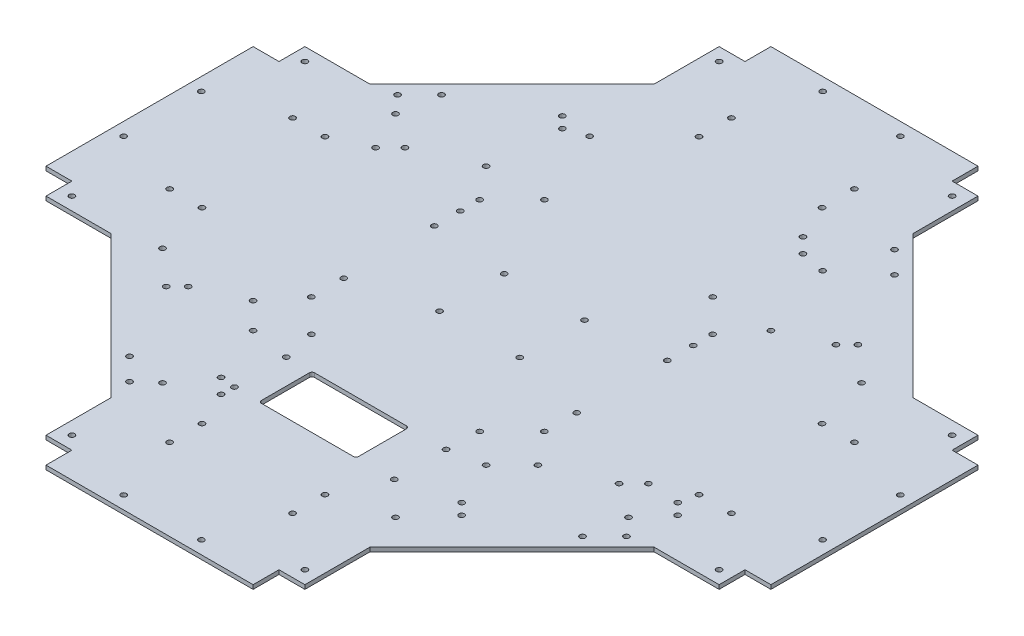
SolidWorks part; units mm, degrees
ref_plane "Front Plane" through (0, 0, 0) normal (0, 0, 1) x (1, 0, 0)
ref_plane "Top Plane" through (0, 0, 0) normal (0, 1, 0) x (1, 0, 0)
ref_plane "Right Plane" through (0, 0, 0) normal (1, 0, 0) x (0, 0, -1)
sketch "Sketch1" plane through (0, 0, 0) normal (0, 1, 0) x (1, 0, 0)
  line L0 (0, -280) -> (100, -280)
  line L1 (100, -280) -> (100, -209.6016)
  line L2 (280, -100) -> (209.6016, -100)
  line L3 (0, 0) -> (0, -280) construction
  line L4 (280, 0) -> (280, -100)
  line L5 (-280, 280) -> (280, 280) construction
  line L6 (-280, 280) -> (-280, -280) construction
  line L7 (-280, -280) -> (280, -280) construction
  line L8 (280, 280) -> (280, -280) construction
  line L9 (-280, 280) -> (280, -280) construction
  line L10 (-280, -280) -> (280, 280) construction
  line L11 (100, -209.6016) -> (209.6016, -100)
  line L12 (-280, 0) -> (-280, -100)
  line L13 (-280, -100) -> (-209.6016, -100)
  line L14 (-209.6016, -100) -> (-100, -209.6016)
  line L15 (-100, -280) -> (-100, -209.6016)
  line L16 (0, -280) -> (-100, -280)
  line L17 (0, 280) -> (-100, 280)
  line L18 (-100, 280) -> (-100, 209.6016)
  line L19 (-100, 209.6016) -> (-209.6016, 100)
  line L20 (-280, 100) -> (-209.6016, 100)
  line L21 (-280, 0) -> (-280, 100)
  line L22 (280, 0) -> (280, 100)
  line L23 (280, 100) -> (209.6016, 100)
  line L24 (209.6016, 100) -> (100, 209.6016)
  line L25 (100, 280) -> (100, 209.6016)
  line L26 (0, 280) -> (100, 280)
  line L27 (111.5258, -219.2889) -> (219.2889, -111.5258) construction
  line L28 (219.2889, -111.5258) -> (247.5732, -139.8101) construction
  line L29 (247.5732, -139.8101) -> (139.8101, -247.5732) construction
  line L30 (139.8101, -247.5732) -> (111.5258, -219.2889) construction
  line L31 (-100, -270) -> (100, -270) construction
  line L32 (-90, -280) -> (-90, 280) construction
  line L33 (-75, -75) -> (75, -75) construction
  line L34 (-75, -75) -> (-75, 75) construction
  line L35 (-75, 75) -> (75, 75) construction
  line L36 (75, -75) -> (75, 75) construction
  line L37 (-75, -75) -> (75, 75) construction
  line L38 (-75, 75) -> (75, -75) construction
  line L39 (-100, -260) -> (100, -260) construction
  line L40 (-280, 40) -> (280, 40) construction
  line L41 (0, 280) -> (0, 0) construction
  line L42 (-280, -90) -> (280, -90) construction
  line L43 (-260, -100) -> (-260, 100) construction
  line L44 (0, 0) -> (-280, 0) construction
  arc A0 (100, -280) -> (280, -100) centre (100, -100) ccw construction
  circle A1 centre (-47.5, -192) radius 2.125
  circle A2 centre (-47.5, -217) radius 2.125
  circle A3 centre (47.5, -217) radius 2.125
  circle A4 centre (47.5, -192) radius 2.125
  circle A5 centre (-192, 47.5) radius 2.125
  circle A6 centre (-217, 47.5) radius 2.125
  circle A7 centre (-192, -47.5) radius 2.125
  circle A8 centre (-217, -47.5) radius 2.125
  circle A9 centre (47.5, 192) radius 2.125
  circle A10 centre (47.5, 217) radius 2.125
  circle A11 centre (-47.5, 192) radius 2.125
  circle A12 centre (-47.5, 217) radius 2.125
  circle A13 centre (192, -47.5) radius 2.125
  circle A14 centre (217, -47.5) radius 2.125
  circle A15 centre (192, 47.5) radius 2.125
  circle A16 centre (217, 47.5) radius 2.125
  circle A17 centre (-90, -270) radius 2.125
  circle A18 centre (-30, -270) radius 2.125
  circle A19 centre (30, -270) radius 2.125
  circle A20 centre (90, -270) radius 2.125
  circle A21 centre (-270, 90) radius 2.125
  circle A22 centre (-270, 30) radius 2.125
  circle A23 centre (-270, -30) radius 2.125
  circle A24 centre (-270, -90) radius 2.125
  circle A25 centre (90, 270) radius 2.125
  circle A26 centre (30, 270) radius 2.125
  circle A27 centre (-30, 270) radius 2.125
  circle A28 centre (-90, 270) radius 2.125
  circle A29 centre (270, -90) radius 2.125
  circle A30 centre (270, -30) radius 2.125
  circle A31 centre (270, 30) radius 2.125
  circle A32 centre (270, 90) radius 2.125
  circle A33 centre (-90, -250) radius 2.125
  circle A34 centre (-90, -180) radius 2.125
  circle A35 centre (-90, -110) radius 2.125
  circle A36 centre (-90, -40) radius 2.125
  circle A37 centre (-90, 30) radius 2.125
  circle A38 centre (-90, 50) radius 2.125
  circle A39 centre (-90, 100) radius 2.125 construction
  circle A40 centre (-90, 150) radius 2.125
  circle A41 centre (-90, 200) radius 2.125 construction
  circle A42 centre (-90, 250) radius 2.125
  circle A43 centre (90, -250) radius 2.125
  circle A44 centre (90, -180) radius 2.125
  circle A45 centre (90, -110) radius 2.125
  circle A46 centre (90, -40) radius 2.125
  circle A47 centre (90, 30) radius 2.125
  circle A48 centre (90, 50) radius 2.125
  circle A49 centre (90, 100) radius 2.125 construction
  circle A50 centre (90, 150) radius 2.125
  circle A51 centre (90, 200) radius 2.125 construction
  circle A52 centre (90, 250) radius 2.125
  circle A53 centre (-250, -90) radius 2.125
  circle A54 centre (-180, -90) radius 2.125
  circle A55 centre (-110, -90) radius 2.125
  circle A56 centre (-110, 90) radius 2.125
  circle A57 centre (-180, 90) radius 2.125
  circle A58 centre (-250, 90) radius 2.125
  circle A59 centre (110, -90) radius 2.125
  circle A60 centre (180, -90) radius 2.125
  circle A61 centre (250, -90) radius 2.125
  circle A62 centre (110, 90) radius 2.125
  circle A63 centre (180, 90) radius 2.125
  circle A64 centre (250, 90) radius 2.125
  point P33 (0, 0)
  point P68 (0, 0)
  point P107 (0, 0)
  dimension "D10" = 25
  dimension "4.25" = 4.25
  dimension "D11" = 4.25
  dimension "D16" = 4.25
  dimension "D24" = 4.25
  dimension "D28" = 4.25
  dimension "D32" = 4.25
  dimension "D1" = 560
  dimension "D2" = 90
  dimension "D3" = 280
  dimension "D4" = 4
  dimension "D5" = 100
  dimension "D6" = 155
  dimension "D7" = 152.4
  dimension "D8" = 15
  dimension "D9" = 40
  dimension "D12" = 47.5
  dimension "D13" = 63
  dimension "D15" = 10
  dimension "D17" = 10
  dimension "D18" = 76.2
  dimension "D19" = 150
  dimension "D20" = 150
  dimension "D23" = 10
  dimension "D25" = 10
  dimension "D26" = 300
  dimension "D29" = 10
  dimension "D31" = 20
  dimension "D33" = 10
  dimension "D21" = 4
  dimension "D27" = 5
  dimension "D30" = 5
  dimension "D34" = 3
  dimension "D14" = 4
  dimension "D22" = 4
extrude "Boss-Extrude1" add sketch "Sketch1" along normal blind 3.175 contours L26 L17 L18 L19 L20 L21 L12 L13 L14 L15 L16 L0 L1 L11 L2 L4 L22 L23 L24 L25 region at (0, 0, -0.0137)
sketch "Sketch2" plane through (0, 3.175, 0) normal (0, 1, 0) x (1, 0, 0)
  line L0 (0, 25.5202) -> (0, -25) construction
  line L1 (-31, -25) -> (31, -25) construction
  line L2 (-31, -25) -> (-31, 25) construction
  line L3 (-31, 25) -> (31, 25) construction
  line L4 (31, -25) -> (31, 25) construction
  line L5 (-31, -25) -> (31, 25) construction
  line L6 (-31, 25) -> (31, -25) construction
  line L7 (75, -75) -> (75, 75) construction
  line L8 (-75, -75) -> (75, -75) construction
  line L9 (-75, -75) -> (-75, 75) construction
  line L10 (-75, 75) -> (75, 75) construction
  line L11 (75, -75) -> (75, 75) construction
  line L12 (-75, -75) -> (75, -75) construction
  line L13 (-75, -75) -> (-75, 75) construction
  line L14 (-75, 75) -> (75, 75) construction
  line L15 (-90, 270) -> (-90, -270) construction
  line L16 (-270, 90) -> (270, 90) construction
  line L17 (-40.0349, -135) -> (34.9651, -135) construction
  line L18 (-40.0349, -155.5) -> (34.9651, -155.5)
  line L19 (-40.0349, -155.5) -> (-40.0349, -114.5)
  line L20 (-40.0349, -114.5) -> (34.9651, -114.5)
  line L21 (34.9651, -155.5) -> (34.9651, -114.5)
  line L22 (-40.0349, -155.5) -> (34.9651, -114.5) construction
  line L23 (-40.0349, -114.5) -> (34.9651, -155.5) construction
  line L24 (153.737, -71.0118) -> (187.3311, -37.4177) construction
  line L25 (128.2843, -167.1751) -> (80.1718, -119.0627) construction
  line L26 (92.9289, -202.5305) -> (202.5305, -92.9289)
  line L27 (92.9289, -202.5305) -> (202.5305, -92.9289) construction
  line L28 (170.0036, -125.4558) -> (128.4969, -83.9492) construction
  circle A0 centre (-31, 25) radius 2.125
  circle A1 centre (-31, -25) radius 2.125
  circle A2 centre (31, -25) radius 2.125
  circle A3 centre (31, 25) radius 2.125
  circle A4 centre (-90, 65) radius 2.125
  circle A5 centre (-65, 90) radius 2.125
  circle A6 centre (65, 90) radius 2.125
  circle A7 centre (90, 65) radius 2.125
  circle A8 centre (90, -65) radius 2.125
  circle A9 centre (65, -90) radius 2.125
  circle A10 centre (-65, -90) radius 2.125
  circle A11 centre (-90, -65) radius 2.125
  circle A12 centre (64.0651, -115) radius 2.125
  circle A13 centre (64.0651, -155) radius 2.125
  circle A14 centre (-59.4349, -115) radius 2.125
  circle A15 centre (-59.4349, -155) radius 2.125
  circle A16 centre (174.9533, -120.5061) radius 2.125
  circle A17 centre (191.9239, -103.5355) radius 2.125
  circle A18 centre (153.737, -71.0118) radius 2.125
  circle A19 centre (165.0507, -59.6981) radius 2.125
  circle A20 centre (-71.0118, -153.737) radius 2.125
  circle A21 centre (-59.6981, -165.0507) radius 2.125
  circle A22 centre (-120.5061, -174.9533) radius 2.125
  circle A23 centre (-103.5355, -191.9239) radius 2.125
  circle A24 centre (-153.737, 71.0118) radius 2.125
  circle A25 centre (-165.0507, 59.6981) radius 2.125
  circle A26 centre (-174.9533, 120.5061) radius 2.125
  circle A27 centre (-191.9239, 103.5355) radius 2.125
  circle A28 centre (71.0118, 153.737) radius 2.125
  circle A29 centre (59.6981, 165.0507) radius 2.125
  circle A30 centre (120.5061, 174.9533) radius 2.125
  circle A31 centre (103.5355, 191.9239) radius 2.125
  circle A32 centre (114.1421, -153.033) radius 2.125
  circle A33 centre (105.6569, -144.5477) radius 2.125
  circle A34 centre (-144.5477, -105.6569) radius 2.125
  circle A35 centre (-153.033, -114.1421) radius 2.125
  circle A36 centre (-105.6569, 144.5477) radius 2.125
  circle A37 centre (-114.1421, 153.033) radius 2.125
  circle A38 centre (144.5477, 105.6569) radius 2.125
  circle A39 centre (153.033, 114.1421) radius 2.125
  circle A40 centre (197.5807, -69.5944) radius 2.125
  circle A41 centre (189.0955, -61.1091) radius 2.125
  point P0 (0, 0)
  point P28 (-2.5349, -135)
  point P43 (0, 0)
  point P94 (0, 0)
  point P113 (0, 0)
  dimension "D3" = 4.25
  dimension "D4" = 4.25
  dimension "D5" = 4.25
  dimension "D7" = 4.25
  dimension "D13" = 4.25
  dimension "D16" = 4.25
  dimension "D20" = 4.25
  dimension "D22" = 4.25
  dimension "D25" = 4.25
  dimension "D26" = 53.85
  dimension "D27" = 4.25
  dimension "D31" = 4.25
  dimension "D32" = 4.25
  dimension "D1" = 62
  dimension "D2" = 50
  dimension "D6" = 10
  dimension "D8" = 10
  dimension "D10" = 41
  dimension "D11" = 75
  dimension "D12" = 135
  dimension "D14" = 20
  dimension "D15" = 66.6
  dimension "D17" = 19.4
  dimension "D18" = 20
  dimension "D21" = 116
  dimension "D23" = 24
  dimension "D24" = 50
  dimension "D28" = 16
  dimension "D30" = 50
  dimension "D33" = 12
  dimension "D34" = 20
  dimension "D36" = 59
  dimension "D19" = 10
  dimension "D9" = 4
  dimension "D29" = 4
  dimension "D35" = 4
extrude "Cut-Extrude1" cut sketch "Sketch2" against normal through all
fillet "Fillet1" radius 2 4 edges at (34.9651, 1.5875, 114.5) (34.9651, 1.5875, 155.5) (-40.0349, 1.5875, 155.5) (-40.0349, 1.5875, 114.5)
sketch "Sketch3" plane through (0, 3.175, 0) normal (0, 1, 0) x (1, 0, 0)
  line L0 (-100, -280) -> (-100, -209.6016) construction
  line L1 (80, -260) -> (100, -260)
  line L2 (80, -260) -> (80, -280)
  line L3 (80, -280) -> (100, -280)
  line L4 (100, -260) -> (100, -280)
  line L5 (80, -260) -> (100, -280) construction
  line L6 (80, -280) -> (100, -260) construction
  line L7 (-80, -260) -> (-100, -260)
  line L8 (-80, -260) -> (-80, -280)
  line L9 (-80, -280) -> (-100, -280)
  line L10 (-100, -260) -> (-100, -280)
  line L11 (-80, -260) -> (-100, -280) construction
  line L12 (-80, -280) -> (-100, -260) construction
  line L13 (100, -280) -> (-100, -280) construction
  line L14 (-260, 80) -> (-280, 80)
  line L15 (-260, 80) -> (-260, 100)
  line L16 (-260, 100) -> (-280, 100)
  line L17 (-280, 80) -> (-280, 100)
  line L18 (-260, -80) -> (-280, -80)
  line L19 (-260, -80) -> (-260, -100)
  line L20 (-260, -100) -> (-280, -100)
  line L21 (-280, -80) -> (-280, -100)
  line L22 (80, 260) -> (80, 280)
  line L23 (80, 260) -> (100, 260)
  line L24 (100, 260) -> (100, 280)
  line L25 (80, 280) -> (100, 280)
  line L26 (-80, 260) -> (-80, 280)
  line L27 (-80, 260) -> (-100, 260)
  line L28 (-100, 260) -> (-100, 280)
  line L29 (-80, 280) -> (-100, 280)
  line L30 (260, -80) -> (280, -80)
  line L31 (260, -80) -> (260, -100)
  line L32 (260, -100) -> (280, -100)
  line L33 (280, -80) -> (280, -100)
  line L34 (260, 80) -> (280, 80)
  line L35 (260, 80) -> (260, 100)
  line L36 (260, 100) -> (280, 100)
  line L37 (280, 80) -> (280, 100)
  point P0 (90, -270)
  point P7 (-90, -270)
  point P44 (0, 0)
extrude "Cut-Extrude2" cut sketch "Sketch3" against normal through all
